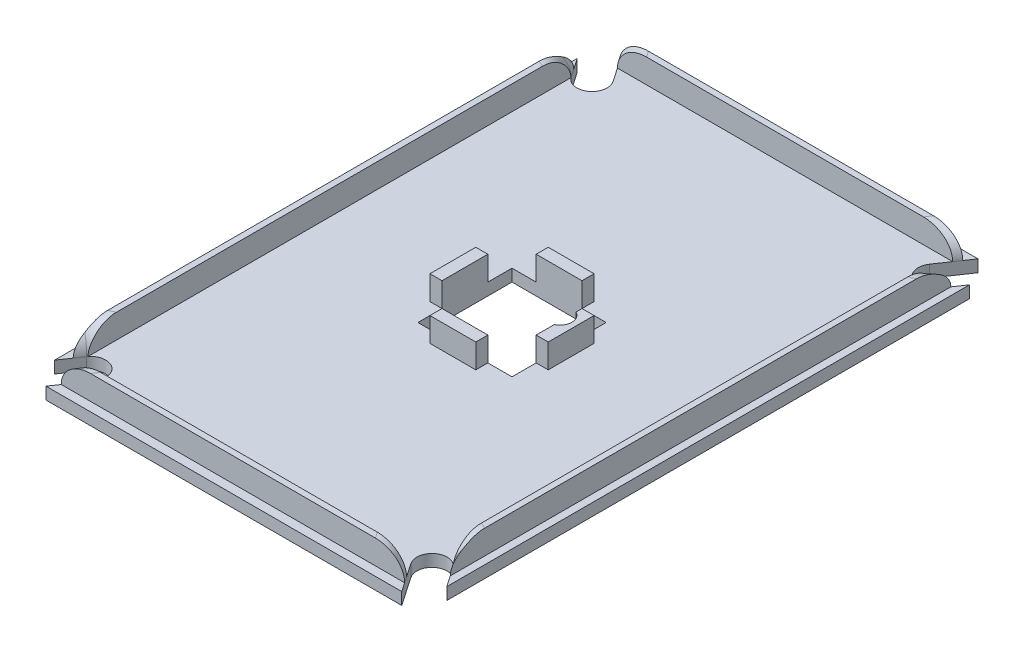
SolidWorks part; units mm, degrees
ref_plane "Front Plane" through (0, 0, 0) normal (0, 0, 1) x (1, 0, 0)
ref_plane "Top Plane" through (0, 0, 0) normal (0, 1, 0) x (1, 0, 0)
ref_plane "Right Plane" through (0, 0, 0) normal (1, 0, 0) x (0, 0, -1)
ref_axis "Axis1" through (0, 14.7, 0) along (0, -1, 0)
sketch "Sketch1" plane through (0, 0, 0) normal (0, 1, 0) x (1, 0, 0)
  line L1 (-31.25, -46.25) -> (31.25, -46.25)
  line L2 (-31.25, -46.25) -> (-31.25, 46.25)
  line L3 (-31.25, 46.25) -> (31.25, 46.25)
  line L4 (31.25, -46.25) -> (31.25, 46.25)
  line L5 (-31.25, -46.25) -> (31.25, 46.25) construction
  line L6 (-31.25, 46.25) -> (31.25, -46.25) construction
  line L7 (-32.5, 47.75) -> (32.5, 47.75)
  line L8 (-32.5, 47.75) -> (-32.5, -47.75)
  line L9 (-32.5, -47.75) -> (32.5, -47.75)
  line L10 (32.5, 47.75) -> (32.5, -47.75)
  line L11 (-32.5, 47.75) -> (32.5, -47.75) construction
  line L12 (-32.5, -47.75) -> (32.5, 47.75) construction
  point P0 (0, 0)
  point P6 (0, 0)
  dimension "D1" = 62.5
  dimension "D2" = 92.5
  dimension "D3" = 65
  dimension "D4" = 95.5
extrude "Boss-Extrude1" add sketch "Sketch1" along normal blind 2 contours L7 L10 L9 L8
extrude "Boss-Extrude2" add sketch "Sketch1<3>" along normal blind 6 contours L1 L4 L3 L2 region at (0, 0, 0)
sketch "Sketch1<3>" plane through (0, 0, 0) normal (0, 1, 0) x (1, 0, 0) same geometry as "Sketch1"
sketch "Sketch2" plane through (0, 0, 0) normal (0, 1, 0) x (1, 0, 0)
  line L0 (7.8, 7.8) -> (7.8, 2.8) construction
  line L1 (-7.8, 7.8) -> (7.8, 7.8)
  line L2 (-7.8, 7.8) -> (-7.8, -7.8)
  line L3 (-7.8, -7.8) -> (7.8, -7.8)
  line L4 (7.8, 7.8) -> (7.8, -7.8)
  line L5 (-7.8, 7.8) -> (7.8, -7.8) construction
  line L6 (-7.8, -7.8) -> (7.8, 7.8) construction
  line L7 (7.8, -7.8) -> (7.8, -0.8) construction
  line L8 (7.8, 2.8) -> (7.8, -0.8)
  line L12 (-9.8, -9.8) -> (9.8, -9.8)
  line L13 (9.8, 9.8) -> (9.8, -9.8)
  line L14 (-9.8, 9.8) -> (9.8, 9.8)
  line L15 (-9.8, 9.8) -> (-9.8, -9.8)
  arc A0 (7.8, -0.8) -> (7.8, 2.8) centre (6.9282, 1) ccw
  circle A1 centre (0, 0) radius 8.15
  point P0 (0, 0)
  dimension "D3" = 4
  dimension "D7" = 16.3
  dimension "D1" = 15.6
  dimension "D2" = 15.6
  dimension "D4" = 5
  dimension "D5" = 7
  dimension "D6" = 2
extrude "Boss-Extrude3" add sketch "Sketch2<4>" along normal blind 6 contours L13 L14 L15 L12
sketch "Sketch2<4>" plane through (0, 0, 0) normal (0, 1, 0) x (1, 0, 0) same geometry as "Sketch2"
extrude "Cut-Extrude2" cut sketch "Sketch2" along normal blind 39 contours L4 A0 | L3 L4 L1 L2 | A0 L8 region at (7.9471, 0, -0.5129)
sketch "Sketch3" plane through (0, 0, 0) normal (0, 1, 0) x (1, 0, 0)
  line L3 (-34.5667, 46.3433) -> (-30.3467, 40.1432)
  line L4 (30.4333, 49.1567) -> (26.2133, 42.9565)
  line L5 (-30.4333, 49.1567) -> (-26.2133, 42.9565)
  line L6 (34.5667, 46.3433) -> (30.3467, 40.1432)
  line L7 (-34.5667, -46.3433) -> (-30.4333, -49.1567)
  line L8 (30.4333, -49.1567) -> (34.5667, -46.3433)
  line L9 (30.4333, 49.1567) -> (34.5667, 46.3433)
  line L10 (-30.4333, 49.1567) -> (-34.5667, 46.3433)
  line L18 (30.3467, -40.1432) -> (34.5667, -46.3433)
  line L20 (0, 23.1046) -> (0, -27.3759) construction
  line L21 (0, -7.7) -> (0, 7.7) construction
  line L22 (26.2133, -42.9565) -> (30.4333, -49.1567)
  line L23 (-26.2133, -42.9565) -> (-30.4333, -49.1567)
  line L24 (-30.3467, -40.1432) -> (-34.5667, -46.3433)
  circle A0 centre (-28.28, 41.5499) radius 2.5
  circle A1 centre (28.28, 41.5499) radius 2.5
  circle A2 centre (-28.28, -41.5499) radius 2.5
  circle A3 centre (28.28, -41.5499) radius 2.5
  point P27 (0, 0)
  dimension "D3" = 5
  dimension "D6" = 5
  dimension "D7" = 5
extrude "Cut-Extrude3" cut sketch "Sketch3" along normal blind 10 contours A2 | A2 L24 L7 L23 | A0 L5 L10 L3 | A0 | A1 L6 L9 L4 | A3 | A3 L22 L8 L18 | A1 region at (-30.9266, 0, -45.4383) region at (-28.28, 0, -41.5499) region at (30.9266, 0, -45.4383) region at (-30.9266, 0, 45.4383) region at (-28.28, 0, 41.5499) region at (30.9266, 0, 45.4383) region at (28.28, 0, 41.5499)
fillet "Fillet1" radius 4 12 edges at (-30.7984, 6, 40.8068) (-27.3341, 6, 44.6033) (27.3341, 6, 44.6033) (30.7984, 6, 40.8068) (30.7984, 6, -40.8068) (27.3341, 6, -44.6033) (-27.3341, 6, -44.6033) (-30.7984, 6, -40.8068) (-26.8733, 6, 39.4832) (26.8733, 6, 39.4832) (26.8733, 6, -39.4832) (-26.8733, 6, -39.4832)
sketch "Sketch5" plane through (0, 6, 0) normal (0, 1, 0) x (1, 0, 0)
  line L16 (-21.7563, -45.25) -> (21.7563, -45.25)
  line L17 (30.25, -34.3132) -> (30.25, 34.3132)
  line L18 (21.7563, 45.25) -> (-21.7563, 45.25)
  line L19 (-30.25, 34.3132) -> (-30.25, -34.3132)
  line L20 (-21.7563, -45.25) -> (21.7563, -45.25)
  line L21 (30.25, -34.3132) -> (30.25, 34.3132)
  line L22 (21.7563, 45.25) -> (-21.7563, 45.25)
  line L23 (-30.25, 34.3132) -> (-30.25, -34.3132)
  line L26 (9.8, -9.8) -> (-9.8, -9.8)
  line L30 (-9.8, 9.8) -> (-9.8, -9.8)
  line L31 (9.8, 9.8) -> (-9.8, 9.8)
  line L32 (9.8, 9.8) -> (9.8, -9.8)
  line L33 (-21.7563, 45.25) -> (-30.25, 45.25)
  line L34 (-30.25, 45.25) -> (-30.25, 34.3132)
  line L35 (21.7563, 45.25) -> (30.25, 45.25)
  line L36 (30.25, 45.25) -> (30.25, 34.3132)
  line L37 (21.7563, -45.25) -> (30.25, -45.25)
  line L38 (30.25, -45.25) -> (30.25, -34.3132)
  line L39 (-30.25, -45.25) -> (-30.25, -34.3132)
  line L40 (-21.7563, -45.25) -> (-30.25, -45.25)
  arc A8 (-21.7563, -45.25) -> (-30.25, -34.3132) centre (-28.28, -41.5499) ccw
  arc A9 (30.25, -34.3132) -> (21.7563, -45.25) centre (28.28, -41.5499) ccw
  arc A10 (21.7563, 45.25) -> (30.25, 34.3132) centre (28.28, 41.5499) ccw
  arc A11 (-30.25, 34.3132) -> (-21.7563, 45.25) centre (-28.28, 41.5499) ccw
  arc A12 (-21.7563, -45.25) -> (-30.25, -34.3132) centre (-28.28, -41.5499) ccw construction
  arc A13 (30.25, -34.3132) -> (21.7563, -45.25) centre (28.28, -41.5499) ccw construction
  arc A14 (21.7563, 45.25) -> (30.25, 34.3132) centre (28.28, 41.5499) ccw construction
  arc A15 (-30.25, 34.3132) -> (-21.7563, 45.25) centre (-28.28, 41.5499) ccw construction
  dimension "D1" = 1
sketch "Sketch7" plane through (0, 0, 0) normal (0, 1, 0) x (1, 0, 0)
  line L0 (7.8, 7.8) -> (7.8, -7.8) construction
  line L1 (7.8, 2.8) -> (7.8, -0.8)
  arc A0 (7.8, -0.8) -> (7.8, 2.8) centre (6.9282, 1) ccw construction
  arc A1 (7.8, -0.8) -> (7.8, 2.8) centre (6.9282, 1) ccw
extrude "Boss-Extrude4" add sketch "Sketch7" along normal blind 1
extrude "Cut-Extrude7" cut sketch "Sketch5" against normal blind 4
sketch "Sketch8" plane through (0, 2, 0) normal (0, 1, 0) x (1, 0, 0)
  line L0 (3.8, 3.8) -> (9.8, 3.8)
  line L1 (-9.8, 9.8) -> (-3.8, 9.8)
  line L2 (-9.8, 9.8) -> (-9.8, 3.8)
  line L3 (-9.8, 3.8) -> (-3.8, 3.8)
  line L4 (-3.8, 9.8) -> (-3.8, 3.8)
  line L5 (9.8, 9.8) -> (9.8, 3.8)
  line L6 (3.8, 9.8) -> (9.8, 9.8)
  line L7 (3.8, 9.8) -> (3.8, 3.8)
  line L8 (-9.8, -9.8) -> (-3.8, -9.8)
  line L9 (9.8, -3.8) -> (9.8, -9.8)
  line L10 (-9.8, -3.8) -> (-3.8, -3.8)
  line L11 (-3.8, -3.8) -> (-3.8, -9.8)
  line L12 (3.8, -3.8) -> (9.8, -3.8)
  line L13 (-9.8, -3.8) -> (-9.8, -9.8)
  line L14 (3.8, -3.8) -> (3.8, -9.8)
  line L15 (3.8, -9.8) -> (9.8, -9.8)
  dimension "D1" = 6
  dimension "D2" = 6
  dimension "D3" = 6
  dimension "D4" = 6
extrude "Cut-Extrude8" cut sketch "Sketch8" along normal blind 10
